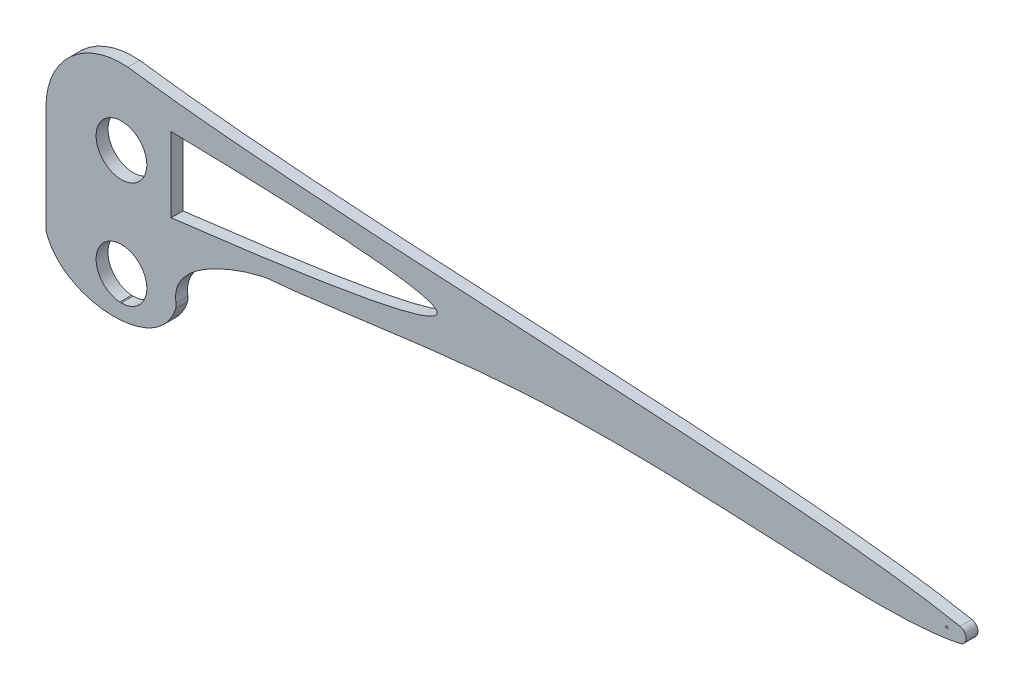
SolidWorks part; units mm, degrees
ref_plane "Front Plane" through (0, 0, 0) normal (0, 0, 1) x (1, 0, 0)
ref_plane "Top Plane" through (0, 0, 0) normal (0, 1, 0) x (1, 0, 0)
ref_plane "Right Plane" through (0, 0, 0) normal (1, 0, 0) x (0, 0, -1)
sketch "Sketch1" plane through (0, 0, 0) normal (0, 0, 1) x (1, 0, 0)
  line L0 (0, 0) -> (0, -35.6856) construction
  line L1 (-25.1919, 0) -> (-25.1919, -35.2154)
  arc A1 (279.8894, 2.3729) -> (279.9348, -2.6026) centre (279.4, -0.1195) cw
  arc A2 (2.0902, 25.105) -> (-25.1919, 0) centre (0, 0) ccw
  circle A5 centre (0, -35.6856) radius 8.4667
  circle A6 centre (0, 0) radius 8.4667
  arc A8 (18.2122, -35.0564) -> (18.1176, -36.6407) centre (14.8556, -35.6511) cw
  arc A9 (-25.1919, -35.2154) -> (-25.0041, -36.3312) centre (-21.783, -35.2154) ccw
  spline S0 degree 3 poles (2.0902, 25.105) (29.3726, 21.3189) (128.0417, 14.5406) (239.5484, 10.2935) (279.8894, 2.3729) knots 0.008543 0.008543 0.008543 0.008543 0.340595 0.941395 0.941395 0.941395 0.941395
  spline S1 degree 3 poles (50.3146, -12.4878) (67.829, -11.2174) (162.8512, 6.0974) (250.0383, -9.0418) (279.9348, -2.6026) knots 0.235846 0.235846 0.235846 0.235846 0.495201 0.941477 0.941477 0.941477 0.941477
  spline S2 degree 3 poles (18.2122, -35.0564) (15.7223, -21.0033) (45.0837, -12.5774) (50.3146, -12.4878) knots 0.243689 0.243689 0.243689 0.243689 1 1 1 1
  spline S3 degree 3 poles (-25.0041, -36.3312) (-24.3022, -38.3573) (-17.5003, -49.4729) (6.4866, -52.353) (16.8283, -40.8908) (18.1176, -36.6407) knots 0.011286 0.011286 0.011286 0.011286 0.130988 0.750185 0.983992 0.983992 0.983992 0.983992
  point P3 (76.2, 0)
  dimension "D1" = 3.4089
  dimension "D2" = 2.54
  dimension "D3" = 16.9333
  dimension "D4" = 35.6856
  dimension "D5" = 305.0812
  dimension "D6" = 279.4
extrude "Boss-Extrude1" add sketch "Sketch1" along normal blind 3.9688 contours S1 A1 S0 region at (77.9982, -1.0618, 0)
scale "Scale1" scale about centroid uniform scaling yes scale factor 0.75
sketch "Sketch2" plane through (0, 0, 3.4727) normal (0, 0, 1) x (1, 0, 0)
  line L0 (31.9233, -8.6699) -> (31.9233, 10.02)
  spline S1 degree 2 poles (31.9233, 10.02) (165.1103, 7.315) (31.9233, -8.6699) knots 0 0 0 1 1 1
extrude "Cut-Extrude1" cut sketch "Sketch2" against normal through all both and the other way through all
sketch "Sketch3" plane through (0, 0, 3.4727) normal (0, 0, 1) x (1, 0, 0)
  circle A0 centre (19.2662, -33.1495) radius 0.2858
  circle A1 centre (226.1269, -0.3747) radius 0.2857
  dimension "D1" = 0.5715
extrude "Cut-Extrude2" cut sketch "Sketch3" against normal through all both
